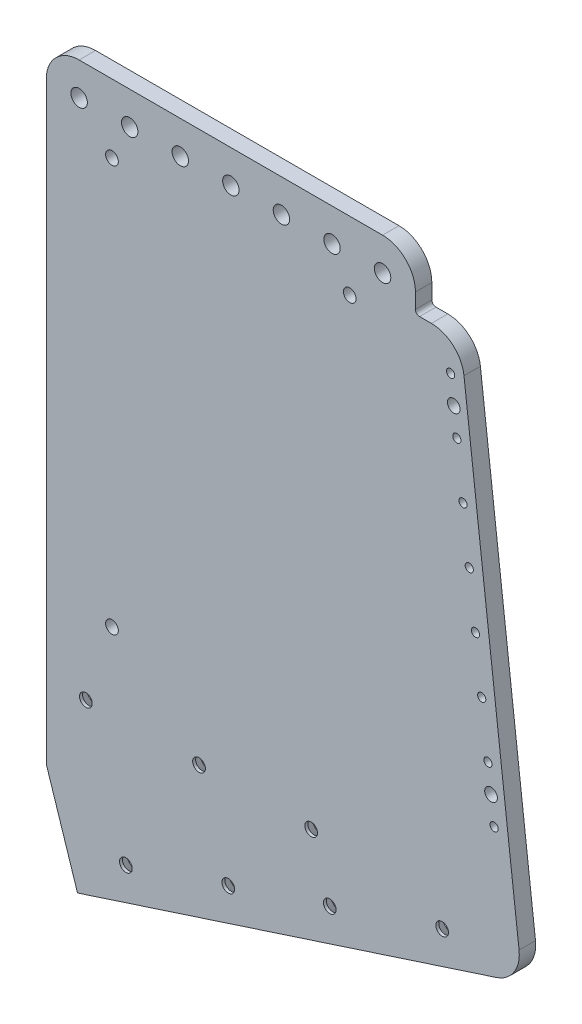
SolidWorks part; units mm, degrees
material "Acrylic (Medium-high impact)"
ref_plane "Front Plane" through (0, 0, 0) normal (0, 0, 1) x (1, 0, 0)
ref_plane "Top Plane" through (0, 0, 0) normal (0, 1, 0) x (1, 0, 0)
ref_plane "Right Plane" through (0, 0, 0) normal (1, 0, 0) x (0, 0, -1)
sketch "Sketch1" plane through (0, 0, 0) normal (0, 0, 1) x (1, 0, 0)
  line L1 (-234.753, 12.7) -> (-91.9973, 12.7)
  line L2 (-234.753, 12.7) -> (-234.753, -270.5428)
  line L3 (-234.753, -270.5428) -> (-50.7003, -210.6746)
  line L4 (-74.5335, -7.417) -> (-50.7003, -210.6746)
  line L5 (-64.9774, -197.966) -> (-88.1902, 0) construction
  line L8 (-74.5335, -7.417) -> (-91.9973, -7.417)
  line L9 (-91.9973, -7.417) -> (-91.9973, 12.7)
  line L10 (-91.9973, 0) -> (-91.9973, 12.7) construction
  dimension "D1" = 12.7
  dimension "D2" = 71.981
  dimension "D3" = 283.2428
extrude "Boss-Extrude1" add sketch "Sketch1" along normal blind 6.35
fillet "Fillet1" radius 12.7 4 edges at (-74.5335, -7.417, 3.175) (-50.7003, -210.6746, 3.175) (-234.753, 12.7, 3.175) (-91.9973, 12.7, 3.175)
sketch "Sketch2" plane through (0, 0, 6.35) normal (0, 0, 1) x (1, 0, 0)
  line L0 (-234.753, -270.5428) -> (-60.5975, -213.8939) construction
  line L1 (-234.753, 0) -> (-234.753, -270.5428) construction
  line L2 (-234.753, -270.5428) -> (-222.6758, -266.6143)
  line L3 (-234.753, -229.4856) -> (-234.753, -270.5428)
  line L4 (-222.6758, -266.6143) -> (-234.753, -229.4856)
  dimension "D1" = 12.7
extrude "Cut-Extrude1" cut sketch "Sketch2" against normal through all
hole_wizard "CSK for #8 Flat Head Machine Screw1" positions "Sketch3" profile "Sketch4" countersink size "#8" standard "ANSI Inch" end condition through all
sketch "Sketch3" plane through (0, 0, 0) normal (0, 0, -1) x (-1, 0, 0)
  point P0 (203.9698, -247.917)
  point P3 (164.3688, -235.0357)
  point P6 (175.687, -200.2402)
  point P9 (219.4388, -200.3608)
  point P12 (125.1181, -222.2683)
  point P15 (132.3222, -200.1207)
  point P18 (81.6603, -208.1325)
sketch "Sketch4" plane through (-203.9698, -247.917, 0) normal (1, 0, 0) x (0, 1, 0)
  line L0 (0, 0) -> (0, 6.35)
  line L1 (0, 6.35) -> (2.4574, 6.35)
  line L2 (2.4574, 6.35) -> (2.4574, 5.1984)
  line L3 (2.4574, 5.1984) -> (6.9764, 0)
  line L5 (6.9764, 0) -> (0, 0)
  line L6 (-2.4575, 5.1984) -> (-6.9764, 0) construction
  line L11 (0, -6.35) -> (0, 107.95) construction
  dimension "Thru Hole Dia." = 4.9149
  dimension "Thru Hole Depth" = 6.35
  dimension "Near C'Sink Dia." = 13.9528
  dimension "Near C'Sink Angle" = 82
sketch "Sketch5" plane through (0, 0, 6.35) normal (0, 0, 1) x (1, 0, 0)
  circle A0 centre (-90.1466, -37.8408) radius 5.5563
  circle A1 centre (-75.5767, -162.098) radius 5.5563
  dimension "D1" = 11.1125
extrude "Cut-Extrude2" [suppressed] cut sketch "Sketch5" against normal up to next
hole_wizard "1/8 (0.125) Diameter Hole1" positions "Sketch6" profile "Sketch7" hole size "1/8" standard "ANSI Inch" end condition through all
sketch "Sketch6" plane through (0, 0, 6.35) normal (0, 0, 1) x (1, 0, 0)
  line L0 (-78.3786, -20.4258) -> (-59.1514, -184.4023) construction
  line L4 (-51.9123, -200.3378) -> (-73.2177, -18.638) construction
  line L5 (-234.495, -184.8332) -> (-53.7824, -184.3891) construction
  point P1 (-78.3786, -20.4258)
  point P21 (-75.9752, -40.9228)
  point P22 (-73.5718, -61.4199)
  point P23 (-71.1684, -81.917)
  point P24 (-68.765, -102.414)
  point P25 (-66.3616, -122.9111)
  point P26 (-63.9582, -143.4082)
  point P27 (-61.5548, -163.9053)
  dimension "D1" = 5.334
  dimension "D2" = 165.1
  dimension "D3" = 8
sketch "Sketch7" plane through (-78.3786, -20.4258, 6.35) normal (1, 0, 0) x (0, -1, 0)
  line L0 (0, 0) -> (0, 6.35)
  line L1 (0, 6.35) -> (1.5875, 6.35)
  line L2 (1.5875, 6.35) -> (1.5875, 0)
  line L5 (1.5875, 0) -> (0, 0)
  line L11 (0, -6.35) -> (0, 107.95) construction
  dimension "Thru Hole Dia." = 3.175
  dimension "Thru Hole Depth" = 6.35
hole_wizard "#8 Clearance Hole1" positions "Sketch8" profile "Sketch9" hole size "#8" standard "ANSI Inch" end condition through all
sketch "Sketch8" plane through (0, 0, 6.35) normal (0, 0, 1) x (1, 0, 0)
  line L0 (-78.3786, -20.4258) -> (-75.9752, -40.9228) construction
  line L2 (-63.9582, -143.4082) -> (-61.5548, -163.9053) construction
  circle A0 centre (-78.3786, -20.4258) radius 1.5875 construction
  circle A1 centre (-75.9752, -40.9228) radius 1.5875 construction
  circle A2 centre (-63.9582, -143.4082) radius 1.5875 construction
  circle A3 centre (-61.5548, -163.9053) radius 1.5875 construction
  point P23 (-62.7565, -153.6567)
  point P25 (-77.1769, -30.6743)
sketch "Sketch9" plane through (-77.1769, -30.6743, 6.35) normal (1, 0, 0) x (0, -1, 0)
  line L0 (0, 0) -> (0, 6.35)
  line L1 (0, 6.35) -> (2.4574, 6.35)
  line L2 (2.4574, 6.35) -> (2.4574, 0)
  line L5 (2.4574, 0) -> (0, 0)
  line L11 (0, -6.35) -> (0, 107.95) construction
  dimension "Thru Hole Dia." = 4.9149
  dimension "Thru Hole Depth" = 6.35
hole_wizard "1/4 (0.25) Diameter Hole1" positions "Sketch10" profile "Sketch11" hole size "1/4" standard "ANSI Inch" end condition through all
sketch "Sketch10" plane through (0, 0, 6.35) normal (0, 0, 1) x (1, 0, 0)
  point P0 (-104.6973, 0)
  point P2 (-124.2566, 0)
  point P4 (-143.8159, 0)
  point P6 (-163.3751, 0)
  point P8 (-182.9344, 0)
  point P10 (-202.4937, 0)
  point P12 (-222.053, 0)
sketch "Sketch11" plane through (-104.6973, 0, 6.35) normal (1, 0, 0) x (0, -1, 0)
  line L0 (0, 0) -> (0, 6.35)
  line L1 (0, 6.35) -> (3.175, 6.35)
  line L2 (3.175, 6.35) -> (3.175, 0)
  line L5 (3.175, 0) -> (0, 0)
  line L11 (0, -6.35) -> (0, 107.95) construction
  dimension "Thru Hole Dia." = 6.35
  dimension "Thru Hole Depth" = 6.35
hole_wizard "#8 Clearance Hole2" positions "Sketch12" profile "Sketch13" hole size "#8" standard "ANSI Inch" end condition through all
sketch "Sketch12" plane through (0, 0, 6.35) normal (0, 0, 1) x (1, 0, 0)
  point P1 (-117.3973, -13.767)
  point P3 (-209.353, -13.767)
sketch "Sketch13" plane through (-117.3973, -13.767, 6.35) normal (1, 0, 0) x (0, -1, 0)
  line L0 (0, 0) -> (0, 6.35)
  line L1 (0, 6.35) -> (2.4574, 6.35)
  line L2 (2.4574, 6.35) -> (2.4574, 0)
  line L5 (2.4574, 0) -> (0, 0)
  line L11 (0, -6.35) -> (0, 107.95) construction
  dimension "Thru Hole Dia." = 4.9149
  dimension "Thru Hole Depth" = 6.35
hole_wizard "#8 Clearance Hole3" positions "Sketch14" profile "Sketch15" hole size "#8" standard "ANSI Inch" end condition through all
sketch "Sketch14" plane through (0, 0, 6.35) normal (0, 0, 1) x (1, 0, 0)
  line L0 (-209.353, -13.767) -> (-209.353, -262.2807) construction
  line L1 (-222.6758, -266.6143) -> (-60.5975, -213.8939) construction
  line L2 (-62.7565, -153.6567) -> (-209.353, -170.8461) construction
  line L4 (-51.9123, -200.3378) -> (-73.2177, -18.638) construction
  circle A0 centre (-209.353, -13.767) radius 2.4574 construction
  point P0 (-209.353, -170.8461)
sketch "Sketch15" plane through (-209.353, -170.8461, 6.35) normal (1, 0, 0) x (0, -1, 0)
  line L0 (0, 0) -> (0, 6.35)
  line L1 (0, 6.35) -> (2.4574, 6.35)
  line L2 (2.4574, 6.35) -> (2.4574, 0)
  line L5 (2.4574, 0) -> (0, 0)
  line L11 (0, -6.35) -> (0, 107.95) construction
  dimension "Thru Hole Dia." = 4.9149
  dimension "Thru Hole Depth" = 6.35
fillet "Fillet2" radius 1.5875 1 edges at (-91.9973, -7.417, 3.175)
